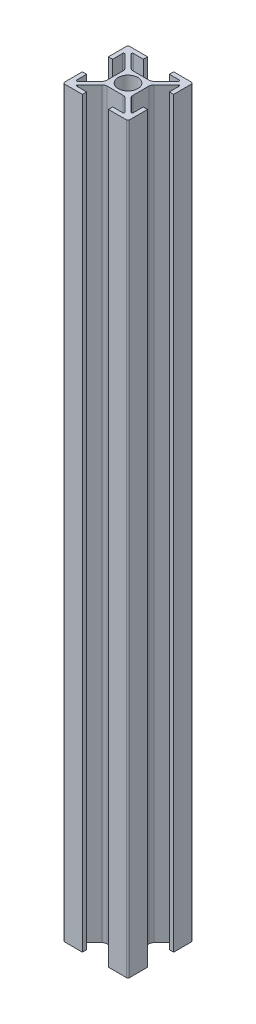
SolidWorks part; units mm, degrees
ref_plane "Plano frontal" through (0, 0, 0) normal (0, 0, 1) x (1, 0, 0)
ref_plane "Plano superior" through (0, 0, 0) normal (0, 1, 0) x (1, 0, 0)
ref_plane "Plano direito" through (0, 0, 0) normal (1, 0, 0) x (0, 0, -1)
sketch "Esboço1" plane through (0, 0, 0) normal (0, 1, 0) x (1, 0, 0)
  line L0 (-7.0565, 8.7) -> (-4, 8.7)
  line L1 (-4, 8.7) -> (-4, 10)
  line L2 (-4, 10) -> (-9.5, 10)
  line L3 (-10, 9.5) -> (-10, 4)
  line L4 (-10, 4) -> (-8.7, 4)
  line L5 (-8.7, 4) -> (-8.7, 7.0565)
  line L6 (-8.1879, 7.2686) -> (-4.4393, 3.5201)
  line L7 (-4, 2.4594) -> (-4, -2.4594)
  line L8 (-4.4393, -3.5201) -> (-8.1879, -7.2686)
  line L9 (-8.7, -7.0565) -> (-8.7, -4)
  line L10 (-8.7, -4) -> (-10, -4)
  line L11 (-10, -4) -> (-10, -9.5)
  line L12 (-9.5, -10) -> (-4, -10)
  line L13 (-4, -10) -> (-4, -8.7)
  line L14 (-4, -8.7) -> (-7.0565, -8.7)
  line L15 (-7.2686, -8.1879) -> (-3.5201, -4.4393)
  line L16 (-2.4594, -4) -> (2.4594, -4)
  line L17 (3.5201, -4.4393) -> (7.2686, -8.1879)
  line L18 (7.0565, -8.7) -> (4, -8.7)
  line L19 (4, -8.7) -> (4, -10)
  line L20 (4, -10) -> (9.5, -10)
  line L21 (10, -9.5) -> (10, -4)
  line L22 (10, -4) -> (8.7, -4)
  line L23 (8.7, -4) -> (8.7, -7.0565)
  line L24 (8.1879, -7.2686) -> (4.4393, -3.5201)
  line L25 (4, -2.4594) -> (4, 2.4594)
  line L26 (4.4393, 3.5201) -> (8.1879, 7.2686)
  line L27 (8.7, 7.0565) -> (8.7, 4)
  line L28 (8.7, 4) -> (10, 4)
  line L29 (10, 4) -> (10, 9.5)
  line L30 (9.5, 10) -> (4, 10)
  line L31 (4, 10) -> (4, 8.7)
  line L32 (4, 8.7) -> (7.0565, 8.7)
  line L33 (7.2686, 8.1879) -> (3.5201, 4.4393)
  line L34 (2.4594, 4) -> (-2.4594, 4)
  line L35 (-3.5201, 4.4393) -> (-7.2686, 8.1879)
  circle A0 centre (0, 0) radius 3
  arc A1 (-7.0565, 8.7) -> (-7.2686, 8.1879) centre (-7.0565, 8.4) ccw
  arc A2 (-9.5, 10) -> (-10, 9.5) centre (-9.5, 9.5) ccw
  arc A3 (-8.1879, 7.2686) -> (-8.7, 7.0565) centre (-8.4, 7.0565) ccw
  arc A4 (-4, 2.4594) -> (-4.4393, 3.5201) centre (-5.5, 2.4594) ccw
  arc A5 (-4.4393, -3.5201) -> (-4, -2.4594) centre (-5.5, -2.4594) ccw
  arc A6 (-8.7, -7.0565) -> (-8.1879, -7.2686) centre (-8.4, -7.0565) ccw
  arc A7 (-10, -9.5) -> (-9.5, -10) centre (-9.5, -9.5) ccw
  arc A8 (-7.2686, -8.1879) -> (-7.0565, -8.7) centre (-7.0565, -8.4) ccw
  arc A9 (-2.4594, -4) -> (-3.5201, -4.4393) centre (-2.4594, -5.5) ccw
  arc A10 (3.5201, -4.4393) -> (2.4594, -4) centre (2.4594, -5.5) ccw
  arc A11 (7.0565, -8.7) -> (7.2686, -8.1879) centre (7.0565, -8.4) ccw
  arc A12 (9.5, -10) -> (10, -9.5) centre (9.5, -9.5) ccw
  arc A13 (8.1879, -7.2686) -> (8.7, -7.0565) centre (8.4, -7.0565) ccw
  arc A14 (4, -2.4594) -> (4.4393, -3.5201) centre (5.5, -2.4594) ccw
  arc A15 (4.4393, 3.5201) -> (4, 2.4594) centre (5.5, 2.4594) ccw
  arc A16 (8.7, 7.0565) -> (8.1879, 7.2686) centre (8.4, 7.0565) ccw
  arc A17 (10, 9.5) -> (9.5, 10) centre (9.5, 9.5) ccw
  arc A18 (7.2686, 8.1879) -> (7.0565, 8.7) centre (7.0565, 8.4) ccw
  arc A19 (2.4594, 4) -> (3.5201, 4.4393) centre (2.4594, 5.5) ccw
  arc A20 (-3.5201, 4.4393) -> (-2.4594, 4) centre (-2.4594, 5.5) ccw
extrude "Ressalto-extrusão1" add sketch "Esboço1" along normal blind 228
